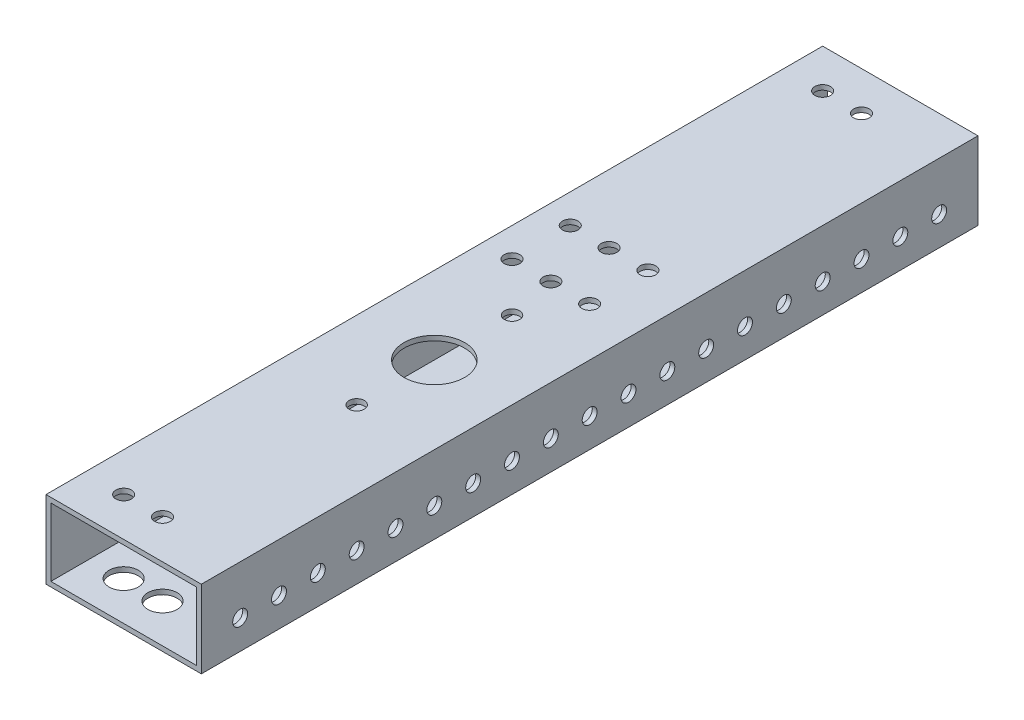
SolidWorks part; units mm, degrees
other "Markup1"
sketch "Sketch7" plane through (25.4, 12.7, -127) normal (0.9965, 0.0171, -0.0817) x (-0.082, 0.0128, -0.9966)
sketch "Sketch8" plane through (25.4, 12.7, -127) normal (0.9965, 0.0171, -0.0817) x (-0.082, 0.0128, -0.9966)
sketch "Sketch9" plane through (25.4, 12.7, -127) normal (0.9965, 0.0171, -0.0817) x (-0.082, 0.0128, -0.9966)
sketch "Sketch12" plane through (25.4, 12.7, -127) normal (0.9965, 0.0171, -0.0817) x (-0.082, 0.0128, -0.9966)
sketch "Sketch13" plane through (25.4, 12.7, -127) normal (0.9965, 0.0171, -0.0817) x (-0.082, 0.0128, -0.9966)
material "6061-T6 (SS)"
ref_plane "Front Plane" through (0, 0, 0) normal (0, 0, 1) x (1, 0, 0)
ref_plane "Top Plane" through (0, 0, 0) normal (0, 1, 0) x (1, 0, 0)
ref_plane "Right Plane" through (0, 0, 0) normal (1, 0, 0) x (0, 0, -1)
sketch "Sketch1" plane through (0, 0, 0) normal (0, 0, 1) x (1, 0, 0)
  line L0 (-23.8125, 11.1125) -> (23.8125, 11.1125)
  line L1 (-25.4, -12.7) -> (25.4, -12.7)
  line L2 (-25.4, -12.7) -> (-25.4, 12.7)
  line L3 (-25.4, 12.7) -> (25.4, 12.7)
  line L4 (25.4, -12.7) -> (25.4, 12.7)
  line L5 (-25.4, -12.7) -> (25.4, 12.7) construction
  line L6 (-25.4, 12.7) -> (25.4, -12.7) construction
  line L7 (23.8125, -11.1125) -> (23.8125, 11.1125)
  line L8 (-23.8125, -11.1125) -> (23.8125, -11.1125)
  line L9 (-23.8125, -11.1125) -> (-23.8125, 11.1125)
  point P0 (0, 0)
  dimension "D1" = 50.8
  dimension "D2" = 25.4
  dimension "D3" = 1.5875
extrude "Boss-Extrude1" add sketch "Sketch1" along normal mid plane 254
sketch "Sketch3" plane through (0, 12.7, 0) normal (0, 1, 0) x (1, 0, 0)
  line L0 (25.4, 127) -> (-25.4, 127) construction
  line L1 (25.4, -127) -> (-25.4, -127) construction
  line L3 (-25.4, -127) -> (-25.4, 127) construction
  line L4 (25.4, -127) -> (25.4, 127) construction
  circle A0 centre (-12.7, -114.3) radius 2.5527
  circle A1 centre (0, -114.3) radius 2.5527
  circle A2 centre (-12.7, 114.3) radius 2.5527
  circle A3 centre (0, 114.3) radius 2.5527
  dimension "D5" = 5.1054
  dimension "D1" = 12.7
  dimension "D2" = 12.7
  dimension "D3" = 12.7
  dimension "D4" = 12.7
  dimension "D6" = 12.7
  dimension "D7" = 12.7
  dimension "D8" = 12.7
  dimension "D9" = 25.4
  dimension "D10" = 12.7
  dimension "D11" = 25.4
extrude "Cut-Extrude1" cut sketch "Sketch3" against normal up to surface (1.5875 mm away) up to face at (0, 11.1125, 0)
sketch "Sketch5" plane through (0, -12.7, 0) normal (0, -1, 0) x (1, 0, 0)
  circle A0 centre (-12.7, -114.3) radius 2.5527 construction
  circle A1 centre (0, -114.3) radius 2.5527 construction
  circle A2 centre (0, 114.3) radius 2.5527 construction
  circle A3 centre (-12.7, 114.3) radius 2.5527 construction
  circle A4 centre (-12.7, -114.3) radius 2.5527
  circle A5 centre (0, -114.3) radius 2.5527
  circle A6 centre (0, 114.3) radius 2.5527
  circle A7 centre (-12.7, 114.3) radius 2.5527
  circle A8 centre (-12.7, 114.3) radius 4.7625
  circle A9 centre (0, 114.3) radius 4.7625
  circle A10 centre (0, -114.3) radius 4.7625
  circle A11 centre (-12.7, -114.3) radius 4.7625
  dimension "D1" = 9.525
extrude "Cut-Extrude2" cut sketch "Sketch5" against normal up to surface (1.5875 mm away) contours A10 A5 | A5 | A11 A4 | A4 | A6 | A9 A6 | A8 A7 | A7 region at (-12.7, -12.7, -114.3) region at (0, -12.7, -114.3) region at (0, -12.7, 114.3) region at (-12.7, -12.7, 114.3) region at (-17.3278, -12.7, 114.3) region at (-4.6278, -12.7, 114.3) region at (-4.6278, -12.7, -114.3) region at (-17.3278, -12.7, -114.3) up to face at (0, -11.1125, 0)
sketch "Sketch6" plane through (25.4, 0, 0) normal (1, 0, 0) x (0, 0, -1)
  line L0 (-127, -12.7) -> (-127, 12.7) construction
  line L1 (-127, -12.7) -> (127, -12.7) construction
  line L2 (0, 12.7) -> (0, -12.7) construction
  line L3 (-127, 12.7) -> (127, 12.7) construction
  circle A0 centre (-114.3, -3.175) radius 2.4384
  circle A1 centre (-101.6, -3.175) radius 2.4384
  circle A2 centre (-88.9, -3.175) radius 2.4384
  circle A3 centre (88.9, -3.175) radius 2.4384
  circle A4 centre (101.6, -3.175) radius 2.4384
  circle A5 centre (114.3, -3.175) radius 2.4384
  circle A6 centre (-76.2, -3.175) radius 2.4384
  circle A7 centre (-63.5, -3.175) radius 2.4384
  circle A8 centre (-50.8, -3.175) radius 2.4384
  circle A9 centre (-38.1, -3.175) radius 2.4384
  circle A10 centre (-25.4, -3.175) radius 2.4384
  circle A11 centre (-12.7, -3.175) radius 2.4384
  circle A12 centre (0, -3.175) radius 2.4384
  circle A13 centre (12.7, -3.175) radius 2.4384
  circle A14 centre (25.4, -3.175) radius 2.4384
  circle A15 centre (38.1, -3.175) radius 2.4384
  circle A16 centre (50.8, -3.175) radius 2.4384
  circle A17 centre (63.5, -3.175) radius 2.4384
  circle A18 centre (76.2, -3.175) radius 2.4384
  dimension "D1" = 4.8768
  dimension "D7" = 4.8768
  dimension "D2" = 12.7
  dimension "D3" = 9.525
  dimension "D4" = 12.7
  dimension "D5" = 12.7
  dimension "D6" = 12.7
  dimension "D8" = 9.525
  dimension "D10" = 12.7
  dimension "D9" = 13
extrude "Cut-Extrude3" cut sketch "Sketch6" against normal up to surface (1.5875 mm away) contours A5 | A4 | A3 | A0 | A1 | A2 | A6 | A7 | A8 | A9 | A10 | A11 | A12 L2 | L2 A12 | A13 | A14 | A15 | A16 | A17 | A18 | A12 region at (25.4, -3.175, -1.0349) region at (25.4, -3.175, 1.0349) region at (25.4, -3.175, 114.3) region at (25.4, -3.175, 101.6) region at (25.4, -3.175, 88.9) region at (25.4, -3.175, -88.9) region at (25.4, -3.175, -101.6) region at (25.4, -3.175, -114.3) region at (25.4, -3.175, 76.2) region at (25.4, -3.175, 63.5) region at (25.4, -3.175, 50.8) region at (25.4, -3.175, 38.1) region at (25.4, -3.175, 25.4) region at (25.4, -3.175, 12.7) region at (25.4, -3.175, -12.7) region at (25.4, -3.175, -25.4) region at (25.4, -3.175, -38.1) region at (25.4, -3.175, -50.8) region at (25.4, -3.175, -63.5) region at (25.4, -3.175, -76.2) up to face at (23.8125, 0, 0)
sketch "Sketch11" plane through (0, 12.7, 0) normal (0, 1, 0) x (1, 0, 0)
  line L0 (-25.4, -127) -> (-25.4, 127) construction
  line L2 (0, 0) -> (0, -50.8) construction
  line L3 (25.4, 127) -> (-25.4, 127) construction
  line L5 (-15.875, 34.925) -> (9.525, 34.925) construction
  line L6 (-15.875, 34.925) -> (-15.875, 15.875) construction
  line L7 (-15.875, 15.875) -> (9.525, 15.875) construction
  line L8 (9.525, 34.925) -> (9.525, 15.875) construction
  line L9 (-15.875, 34.925) -> (9.525, 15.875) construction
  line L10 (-15.875, 15.875) -> (9.525, 34.925) construction
  circle A0 centre (0, -25.4) radius 9.906
  circle A1 centre (0, 0) radius 2.4892
  circle A2 centre (0, -50.8) radius 2.4892
  circle A3 centre (9.525, 15.875) radius 2.5527
  circle A4 centre (-15.875, 15.875) radius 2.5527
  circle A5 centre (-15.875, 34.925) radius 2.5527
  circle A6 centre (9.525, 34.925) radius 2.5527
  circle A7 centre (-3.175, 15.875) radius 2.5527
  circle A8 centre (-3.175, 34.925) radius 2.5527
  point P2 (0, -25.4)
  point P8 (-3.175, 25.4)
  dimension "D1" = 19.812
  dimension "D3" = 4.9784
  dimension "D4" = 25.4
  dimension "D5" = 5.1054
  dimension "D6" = 25.4
  dimension "D7" = 19.05
  dimension "D2" = 152.4
  dimension "D8" = 101.6
  dimension "D9" = 9.525
extrude "Cut-Extrude4" cut sketch "Sketch11" against normal through all
